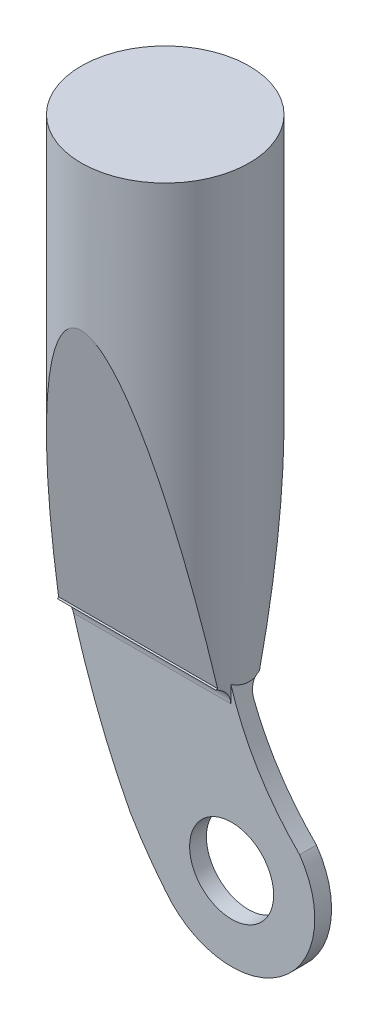
SolidWorks part; units mm, degrees
ref_plane "Front Plane" through (0, 0, 0) normal (0, 0, 1) x (1, 0, 0)
ref_plane "Top Plane" through (0, 0, 0) normal (0, 1, 0) x (1, 0, 0)
ref_plane "Right Plane" through (0, 0, 0) normal (1, 0, 0) x (0, 0, -1)
sketch "Sketch1" plane through (0, 0, 0) normal (0, 1, 0) x (1, 0, 0)
  circle A0 centre (0, 0) radius 12.7
  dimension "D1" = 25.4
extrude "Boss-Extrude1" add sketch "Sketch1" along normal blind 91.44
sketch "Sketch2" plane through (0, 0, 0) normal (0, 0, 1) x (1, 0, 0)
  line L1 (-19.6693, 24.2677) -> (23.4504, 24.2677)
  line L2 (-19.6693, 24.2677) -> (-19.6693, -13.3297)
  line L3 (-19.6693, -13.3297) -> (23.4504, -13.3297)
  line L4 (23.4504, 24.2677) -> (23.4504, -13.3297)
extrude "Cut-Extrude1" cut sketch "Sketch2" against normal blind 66.372
ref_plane "Plane1" through (0, 0, 2.54) normal (0, 0, -1) x (-1, 0, 0)
sketch "Sketch3" plane through (0, 0, 2.54) normal (0, 0, -1) x (-1, 0, 0)
  line L1 (12.0192, 24.3434) -> (-46.6906, 24.3434)
  line L2 (12.0192, 24.3434) -> (12.0192, -15.6054)
  line L3 (12.0192, -15.6054) -> (-46.6906, -15.6054)
  line L4 (-46.6906, 24.3434) -> (-46.6906, -15.6054)
extrude "Cut-Extrude2" cut sketch "Sketch3" against normal blind 11
sketch "Sketch4" plane through (0, 0, 2.54) normal (0, 0, 1) x (1, 0, 0)
  line L0 (12.4434, 0) -> (12.7, 0) construction
  line L1 (-12.0192, 24.3434) -> (12.4434, 24.3434)
  arc A0 (2.5213, -7.5522) -> (20.5264, 9.735) centre (12.5717, 0) ccw
  spline S0 degree 2 poles (-12.0192, 24.3434) (-7.6963, 4.8819) (2.5213, -7.5522) knots 0 0 0 1 1 1
  spline S1 degree 2 poles (12.4434, 24.3434) (15.5042, 14.5395) (22.8508, 7.238) knots 0 0 0 1 1 1
  line M1 (12.4434, 0) -> (12.4434, 24.3434)
  line M4 (-12.0192, 0) -> (12.4434, 0)
extrude "Boss-Extrude2" add sketch "Sketch4" against normal up to surface (2.54 mm away) contours S1 S0 A0 M1 M4 region at (14.0725, -0.3456, 2.54) up to face at (0, 12.1338, 0)
sketch "Sketch5" plane through (0, 0, 2.54) normal (0, 0, 1) x (1, 0, 0)
  line L0 (-12.0192, 24.3434) -> (-30.9939, 25.7174)
  line L1 (-30.9939, 25.7174) -> (-33.2862, -5.9394)
  line L2 (-33.2862, -5.9394) -> (-12.0192, -9.1236)
  line L3 (-12.0192, -9.1236) -> (-2.7611, 0)
  spline S0 degree 2 poles (-2.7611, 0) (-8.4628, 10.868) (-12.0192, 24.3434) knots 0 0 0 1 1 1
extrude "Cut-Extrude7" cut sketch "Sketch5" against normal blind 11
sketch "Sketch6" plane through (0, 0, 2.54) normal (0, 0, -1) x (-1, 0, 0)
  line L4 (12.4434, 24.3742) -> (12.0192, 24.3434)
  line L5 (12.0192, 24.3434) -> (12.0192, 0)
  line L6 (12.0192, 0) -> (12.4434, 0)
  line L7 (12.4434, 0) -> (12.4434, 24.3742)
  line L8 (12.4434, 24.3742) -> (12.0192, 24.3434)
  line L9 (12.0192, 24.3434) -> (12.0192, 0)
  line L10 (12.0192, 0) -> (12.4434, 0)
  line L11 (12.4434, 0) -> (12.4434, 24.3742)
  dimension "D1" = 0
extrude "Cut-Extrude8" cut sketch "Sketch6" against normal blind 11
fillet "Fillet1" radius 2.54 2 edges at (0.2121, 24.3434, 2.54) (0.3504, 24.2677, 0)
sketch "Sketch7" plane through (0, 0, 0) normal (1, 0, 0) x (0, 0, -1)
  line L0 (-4.1024, 24.3434) -> (-12.7, 69.5263)
  line L1 (-12.7, 91.44) -> (-12.7, 24.3434) construction
  line L2 (-12.7, 69.5263) -> (-28.1227, 69.5263)
  line L3 (-28.1227, 69.5263) -> (-24.6481, 13.5465)
  line L4 (-24.6481, 13.5465) -> (-4.1024, 24.3434)
extrude "Cut-Extrude9" cut sketch "Sketch7" against normal mid plane 33.86
sketch "Sketch8" plane through (0, 0, 0) normal (1, 0, 0) x (0, 0, -1)
  line L0 (1.6453, 24.1049) -> (15.2453, 74.7694)
  line L1 (15.2453, 74.7694) -> (33.1533, 74.7694)
  line L2 (33.1533, 74.7694) -> (33.1533, 5.6958)
  line L3 (33.1533, 5.6958) -> (1.6453, 24.1049)
  arc A0 (2.54, 24.2677) -> (0.8652, 23.6373) centre (2.54, 21.7277) ccw construction
extrude "Cut-Extrude10" cut sketch "Sketch8" against normal mid plane 33.86
sketch "Sketch9" plane through (0, 0, 0) normal (0, 0, -1) x (-1, 0, 0)
  circle A0 centre (-12.5717, 0) radius 6.35
  dimension "D1" = 12.7
extrude "Cut-Extrude11" cut sketch "Sketch9" against normal blind 33.86
